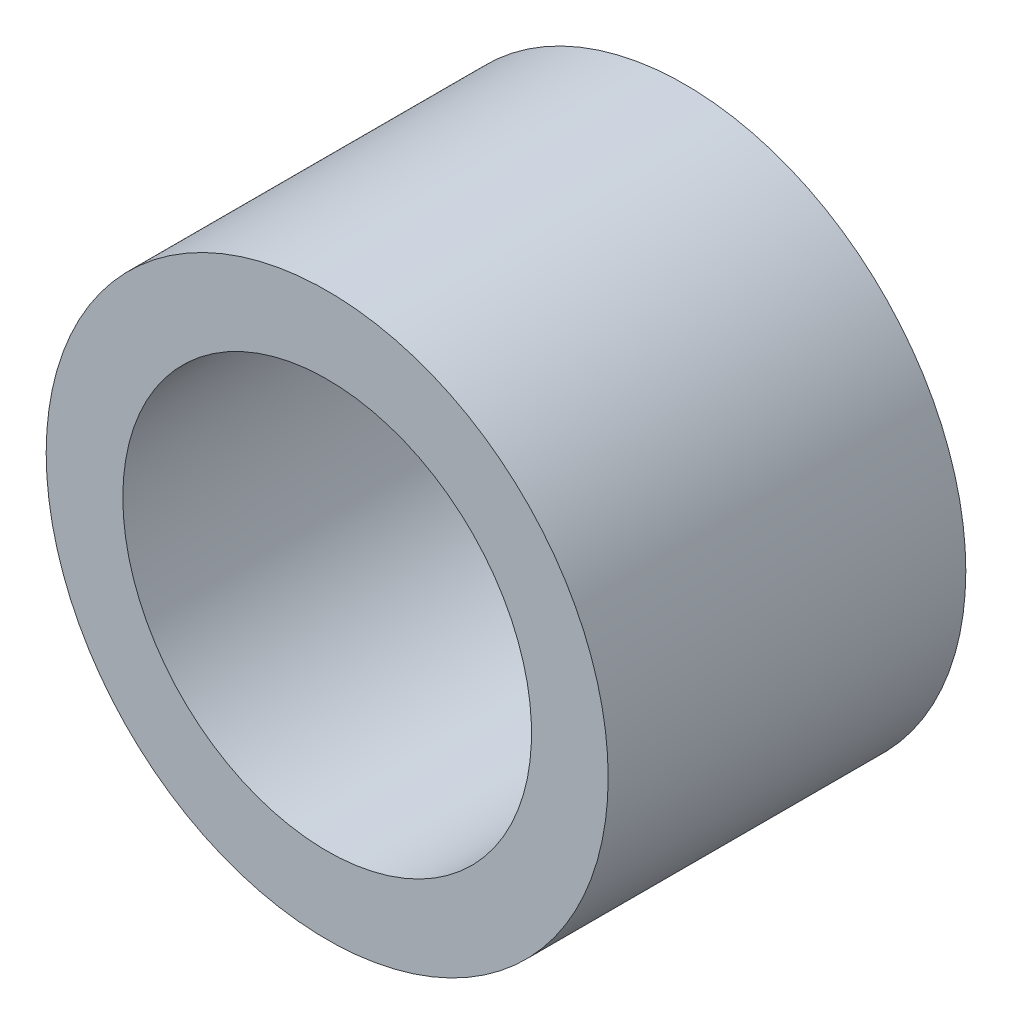
SolidWorks part; units mm, degrees
ref_plane "Front Plane" through (0, 0, 0) normal (0, 0, 1) x (1, 0, 0)
ref_plane "Top Plane" through (0, 0, 0) normal (0, 1, 0) x (1, 0, 0)
ref_plane "Right Plane" through (0, 0, 0) normal (1, 0, 0) x (0, 0, -1)
ref_plane "Plane1" through (0, 0, 11.1199) normal (0, 0, -1) x (-1, 0, 0)
sketch "Sketch1" plane through (0, 0, 11.1199) normal (0, 0, -1) x (-1, 0, 0)
  circle A0 centre (41.5529, -51.3213) radius 5.5
  circle A1 centre (41.5529, -51.3213) radius 16.8 construction
  circle A2 centre (41.5529, -51.3213) radius 4
  dimension "D1" = 11
  dimension "D2" = 8
extrude "Boss-Extrude1" add sketch "Sketch1" along normal up to surface (7 mm away)
